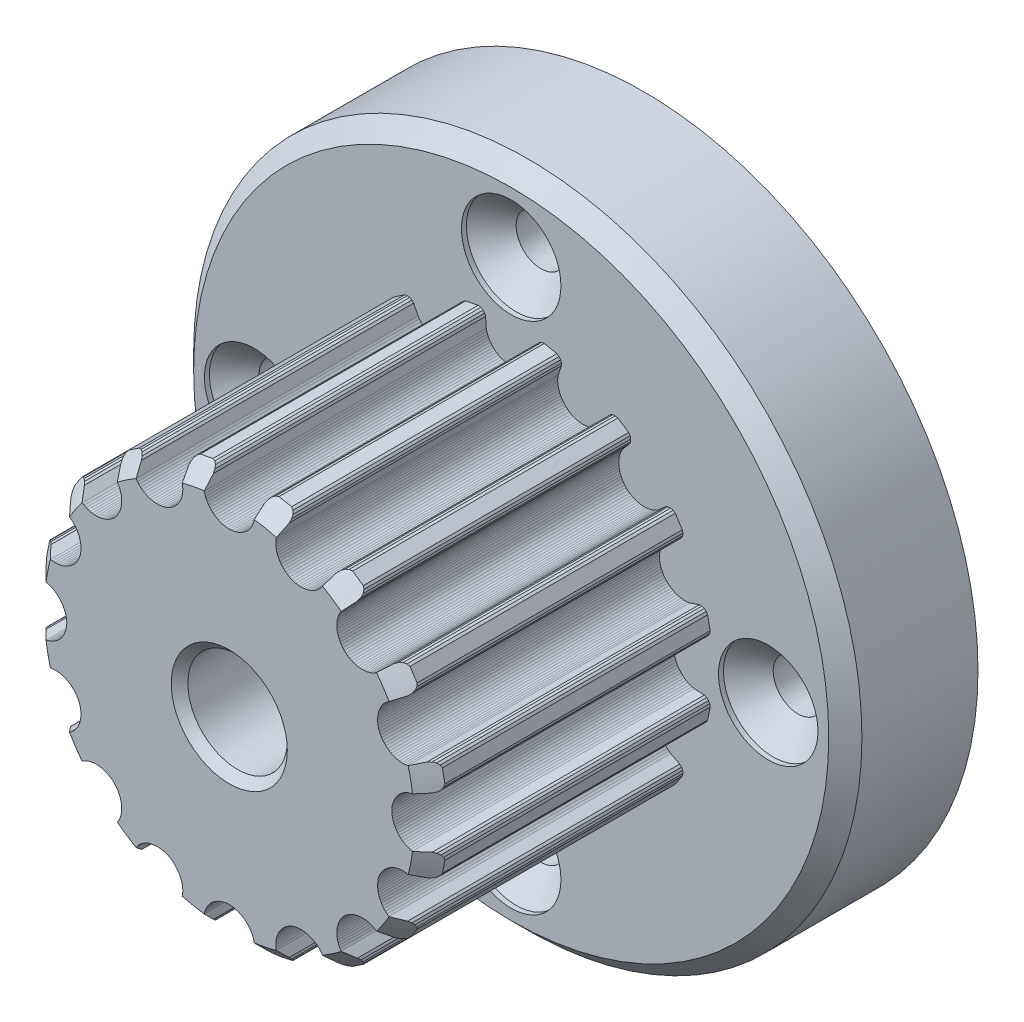
SolidWorks part; units mm, degrees
ref_plane "Front Plane" through (0, 0, 0) normal (0, 0, 1) x (1, 0, 0)
ref_plane "Top Plane" through (0, 0, 0) normal (0, 1, 0) x (1, 0, 0)
ref_plane "Right Plane" through (0, 0, 0) normal (1, 0, 0) x (0, 0, -1)
sketch "Sketch1" plane through (0, 0, 0) normal (0, 0, 1) x (1, 0, 0)
  circle A0 centre (0, 0) radius 15.5
  circle A1 centre (0, 15.5) radius 1.5
  circle A2 centre (15.5, 0) radius 1.5
  circle A3 centre (0, -15.5) radius 1.5
  circle A4 centre (-15.5, 0) radius 1.5
  circle A5 centre (0, 0) radius 20.15
  dimension "D1" = 31
  dimension "D2" = 3
  dimension "D3" = 40.3
extrude "Boss-Extrude1" add sketch "Sketch1" along normal blind 8 contours A5 A4 A0 A1 A2 A3 | A4 A0 A3 A2 A1 region at (0, 0, 0) region at (-19.5801, 0, 0)
sketch "Sketch8" plane through (0, 0, 8) normal (0, 0, 1) x (1, 0, 0)
  line L0 (-1.9904, -11.9969) -> (-1.8333, -11.9702)
  line L1 (-1.8333, -11.9702) -> (-1.6992, -11.8961)
  line L2 (-1.6992, -11.8961) -> (-1.5993, -11.7835)
  line L3 (-1.5993, -11.7835) -> (-1.5446, -11.6413)
  line L4 (-1.5446, -11.6413) -> (-1.5027, -11.0359)
  line L5 (-1.5027, -11.0359) -> (-1.4725, -10.9073)
  line L6 (-1.4725, -10.9073) -> (-1.4313, -10.7834)
  line L7 (-1.4313, -10.7834) -> (-1.3796, -10.6646)
  line L8 (-1.3796, -10.6646) -> (-1.3179, -10.5514)
  line L9 (-1.3179, -10.5514) -> (-1.2467, -10.4444)
  line L10 (-1.2467, -10.4444) -> (-1.1667, -10.3438)
  line L11 (-1.1667, -10.3438) -> (-1.0783, -10.2503)
  line L12 (-1.0783, -10.2503) -> (-0.9822, -10.1642)
  line L13 (-0.9822, -10.1642) -> (-0.8789, -10.086)
  line L14 (-0.8789, -10.086) -> (-0.7689, -10.0162)
  line L15 (-0.7689, -10.0162) -> (-0.6528, -9.9552)
  line L16 (-0.6528, -9.9552) -> (-0.5312, -9.9034)
  line L17 (-0.5312, -9.9034) -> (-0.4045, -9.8614)
  line L18 (-0.4045, -9.8614) -> (-0.2734, -9.8296)
  line L19 (-0.2734, -9.8296) -> (-0.1385, -9.8084)
  line L20 (-0.1385, -9.8084) -> (-0.0002, -9.7984)
  line L21 (-0.0002, -9.7984) -> (0.1382, -9.8084)
  line L22 (0.1382, -9.8084) -> (0.2733, -9.8295)
  line L23 (0.2733, -9.8295) -> (0.4045, -9.8613)
  line L24 (0.4045, -9.8613) -> (0.5312, -9.9032)
  line L25 (0.5312, -9.9032) -> (0.6529, -9.9549)
  line L26 (0.6529, -9.9549) -> (0.7691, -10.0159)
  line L27 (0.7691, -10.0159) -> (0.8791, -10.0858)
  line L28 (0.8791, -10.0858) -> (0.9825, -10.1639)
  line L29 (0.9825, -10.1639) -> (1.0786, -10.25)
  line L30 (1.0786, -10.25) -> (1.1669, -10.3436)
  line L31 (1.1669, -10.3436) -> (1.247, -10.4442)
  line L32 (1.247, -10.4442) -> (1.3181, -10.5512)
  line L33 (1.3181, -10.5512) -> (1.3798, -10.6644)
  line L34 (1.3798, -10.6644) -> (1.4315, -10.7832)
  line L35 (1.4315, -10.7832) -> (1.4726, -10.9072)
  line L36 (1.4726, -10.9072) -> (1.5027, -11.0359)
  line L37 (1.5027, -11.0359) -> (1.5446, -11.6413)
  line L38 (1.5446, -11.6413) -> (1.5993, -11.7835)
  line L39 (1.5993, -11.7835) -> (1.6992, -11.8961)
  line L40 (1.6992, -11.8961) -> (1.8333, -11.9702)
  line L41 (1.8333, -11.9702) -> (1.9904, -11.9969)
  line L42 (1.9904, -11.9969) -> (2.7522, -11.8454)
  line L43 (2.7522, -11.8454) -> (2.8871, -11.7606)
  line L44 (2.8871, -11.7606) -> (2.9825, -11.6408)
  line L45 (2.9825, -11.6408) -> (3.0317, -11.4985)
  line L46 (3.0317, -11.4985) -> (3.0279, -11.3462)
  line L47 (3.0279, -11.3462) -> (2.835, -10.7709)
  line L48 (2.835, -10.7709) -> (2.8136, -10.6405)
  line L49 (2.8136, -10.6405) -> (2.8042, -10.5103)
  line L50 (2.8042, -10.5103) -> (2.8066, -10.3807)
  line L51 (2.8066, -10.3807) -> (2.8203, -10.2526)
  line L52 (2.8203, -10.2526) -> (2.8451, -10.1264)
  line L53 (2.8451, -10.1264) -> (2.8805, -10.0029)
  line L54 (2.8805, -10.0029) -> (2.9264, -9.8827)
  line L55 (2.9264, -9.8827) -> (2.9822, -9.7664)
  line L56 (2.9822, -9.7664) -> (3.0478, -9.6546)
  line L57 (3.0478, -9.6546) -> (3.1227, -9.548)
  line L58 (3.1227, -9.548) -> (3.2066, -9.4472)
  line L59 (3.2066, -9.4472) -> (3.2992, -9.3528)
  line L60 (3.2992, -9.3528) -> (3.4001, -9.2656)
  line L61 (3.4001, -9.2656) -> (3.509, -9.186)
  line L62 (3.509, -9.186) -> (3.6256, -9.1148)
  line L63 (3.6256, -9.1148) -> (3.7495, -9.0526)
  line L64 (3.7495, -9.0526) -> (3.8812, -9.0089)
  line L65 (3.8812, -9.0089) -> (4.0141, -8.9767)
  line L66 (4.0141, -8.9767) -> (4.1474, -8.9558)
  line L67 (4.1474, -8.9558) -> (4.2806, -8.9461)
  line L68 (4.2806, -8.9461) -> (4.4128, -8.9473)
  line L69 (4.4128, -8.9473) -> (4.5435, -8.9592)
  line L70 (4.5435, -8.9592) -> (4.6718, -8.9816)
  line L71 (4.6718, -8.9816) -> (4.7972, -9.0143)
  line L72 (4.7972, -9.0143) -> (4.919, -9.057)
  line L73 (4.919, -9.057) -> (5.0364, -9.1097)
  line L74 (5.0364, -9.1097) -> (5.1488, -9.1719)
  line L75 (5.1488, -9.1719) -> (5.2555, -9.2437)
  line L76 (5.2555, -9.2437) -> (5.3558, -9.3246)
  line L77 (5.3558, -9.3246) -> (5.4491, -9.4146)
  line L78 (5.4491, -9.4146) -> (5.5345, -9.5134)
  line L79 (5.5345, -9.5134) -> (5.6115, -9.6208)
  line L80 (5.6115, -9.6208) -> (5.882, -10.164)
  line L81 (5.882, -10.164) -> (5.9869, -10.2745)
  line L82 (5.9869, -10.2745) -> (6.1223, -10.3403)
  line L83 (6.1223, -10.3403) -> (6.2745, -10.3575)
  line L84 (6.2745, -10.3575) -> (6.4299, -10.322)
  line L85 (6.4299, -10.322) -> (7.0757, -9.8905)
  line L86 (7.0757, -9.8905) -> (7.1679, -9.7605)
  line L87 (7.1679, -9.7605) -> (7.2103, -9.6133)
  line L88 (7.2103, -9.6133) -> (7.2013, -9.4631)
  line L89 (7.2013, -9.4631) -> (7.1394, -9.3238)
  line L90 (7.1394, -9.3238) -> (6.741, -8.8661)
  line L91 (6.741, -8.8661) -> (6.6714, -8.7539)
  line L92 (6.6714, -8.7539) -> (6.6129, -8.6371)
  line L93 (6.6129, -8.6371) -> (6.5655, -8.5165)
  line L94 (6.5655, -8.5165) -> (6.5291, -8.3929)
  line L95 (6.5291, -8.3929) -> (6.5037, -8.2669)
  line L96 (6.5037, -8.2669) -> (6.4892, -8.1392)
  line L97 (6.4892, -8.1392) -> (6.4856, -8.0106)
  line L98 (6.4856, -8.0106) -> (6.4926, -7.8817)
  line L99 (6.4926, -7.8817) -> (6.5104, -7.7534)
  line L100 (6.5104, -7.7534) -> (6.5388, -7.6262)
  line L101 (6.5388, -7.6262) -> (6.5778, -7.501)
  line L102 (6.5778, -7.501) -> (6.6272, -7.3784)
  line L103 (6.6272, -7.3784) -> (6.687, -7.2591)
  line L104 (6.687, -7.2591) -> (6.7572, -7.1439)
  line L105 (6.7572, -7.1439) -> (6.8377, -7.0335)
  line L106 (6.8377, -7.0335) -> (6.9284, -6.9286)
  line L107 (6.9284, -6.9286) -> (7.0333, -6.8378)
  line L108 (7.0333, -6.8378) -> (7.1438, -6.7572)
  line L109 (7.1438, -6.7572) -> (7.259, -6.6869)
  line L110 (7.259, -6.6869) -> (7.3783, -6.627)
  line L111 (7.3783, -6.627) -> (7.5009, -6.5775)
  line L112 (7.5009, -6.5775) -> (7.6262, -6.5385)
  line L113 (7.6262, -6.5385) -> (7.7533, -6.5101)
  line L114 (7.7533, -6.5101) -> (7.8817, -6.4923)
  line L115 (7.8817, -6.4923) -> (8.0105, -6.4852)
  line L116 (8.0105, -6.4852) -> (8.1392, -6.4889)
  line L117 (8.1392, -6.4889) -> (8.2669, -6.5034)
  line L118 (8.2669, -6.5034) -> (8.3929, -6.5288)
  line L119 (8.3929, -6.5288) -> (8.5165, -6.5652)
  line L120 (8.5165, -6.5652) -> (8.6371, -6.6127)
  line L121 (8.6371, -6.6127) -> (8.7539, -6.6713)
  line L122 (8.7539, -6.6713) -> (8.8661, -6.741)
  line L123 (8.8661, -6.741) -> (9.3238, -7.1394)
  line L124 (9.3238, -7.1394) -> (9.4631, -7.2013)
  line L125 (9.4631, -7.2013) -> (9.6133, -7.2103)
  line L126 (9.6133, -7.2103) -> (9.7605, -7.1679)
  line L127 (9.7605, -7.1679) -> (9.8905, -7.0757)
  line L128 (9.8905, -7.0757) -> (10.322, -6.4299)
  line L129 (10.322, -6.4299) -> (10.3575, -6.2745)
  line L130 (10.3575, -6.2745) -> (10.3403, -6.1223)
  line L131 (10.3403, -6.1223) -> (10.2745, -5.9869)
  line L132 (10.2745, -5.9869) -> (10.164, -5.882)
  line L133 (10.164, -5.882) -> (9.6208, -5.6115)
  line L134 (9.6208, -5.6115) -> (9.5135, -5.5345)
  line L135 (9.5135, -5.5345) -> (9.4148, -5.449)
  line L136 (9.4148, -5.449) -> (9.3248, -5.3558)
  line L137 (9.3248, -5.3558) -> (9.2439, -5.2554)
  line L138 (9.2439, -5.2554) -> (9.1722, -5.1487)
  line L139 (9.1722, -5.1487) -> (9.11, -5.0363)
  line L140 (9.11, -5.0363) -> (9.0574, -4.9189)
  line L141 (9.0574, -4.9189) -> (9.0146, -4.7971)
  line L142 (9.0146, -4.7971) -> (8.9819, -4.6717)
  line L143 (8.9819, -4.6717) -> (8.9595, -4.5434)
  line L144 (8.9595, -4.5434) -> (8.9476, -4.4128)
  line L145 (8.9476, -4.4128) -> (8.9463, -4.2806)
  line L146 (8.9463, -4.2806) -> (8.956, -4.1475)
  line L147 (8.956, -4.1475) -> (8.9767, -4.0143)
  line L148 (8.9767, -4.0143) -> (9.0088, -3.8815)
  line L149 (9.0088, -3.8815) -> (9.0524, -3.7498)
  line L150 (9.0524, -3.7498) -> (9.1147, -3.6258)
  line L151 (9.1147, -3.6258) -> (9.1859, -3.5091)
  line L152 (9.1859, -3.5091) -> (9.2654, -3.4)
  line L153 (9.2654, -3.4) -> (9.3527, -3.299)
  line L154 (9.3527, -3.299) -> (9.447, -3.2064)
  line L155 (9.447, -3.2064) -> (9.5478, -3.1224)
  line L156 (9.5478, -3.1224) -> (9.6544, -3.0475)
  line L157 (9.6544, -3.0475) -> (9.7662, -2.9819)
  line L158 (9.7662, -2.9819) -> (9.8826, -2.926)
  line L159 (9.8826, -2.926) -> (10.0028, -2.8802)
  line L160 (10.0028, -2.8802) -> (10.1263, -2.8448)
  line L161 (10.1263, -2.8448) -> (10.2525, -2.82)
  line L162 (10.2525, -2.82) -> (10.3807, -2.8064)
  line L163 (10.3807, -2.8064) -> (10.5102, -2.8041)
  line L164 (10.5102, -2.8041) -> (10.6405, -2.8135)
  line L165 (10.6405, -2.8135) -> (10.7709, -2.835)
  line L166 (10.7709, -2.835) -> (11.3462, -3.0279)
  line L167 (11.3462, -3.0279) -> (11.4985, -3.0317)
  line L168 (11.4985, -3.0317) -> (11.6408, -2.9825)
  line L169 (11.6408, -2.9825) -> (11.7606, -2.8871)
  line L170 (11.7606, -2.8871) -> (11.8454, -2.7522)
  line L171 (11.8454, -2.7522) -> (11.9969, -1.9904)
  line L172 (11.9969, -1.9904) -> (11.9702, -1.8333)
  line L173 (11.9702, -1.8333) -> (11.8961, -1.6992)
  line L174 (11.8961, -1.6992) -> (11.7835, -1.5993)
  line L175 (11.7835, -1.5993) -> (11.6413, -1.5446)
  line L176 (11.6413, -1.5446) -> (11.0359, -1.5027)
  line L177 (11.0359, -1.5027) -> (10.9073, -1.4725)
  line L178 (10.9073, -1.4725) -> (10.7834, -1.4313)
  line L179 (10.7834, -1.4313) -> (10.6646, -1.3796)
  line L180 (10.6646, -1.3796) -> (10.5514, -1.3179)
  line L181 (10.5514, -1.3179) -> (10.4444, -1.2467)
  line L182 (10.4444, -1.2467) -> (10.3438, -1.1667)
  line L183 (10.3438, -1.1667) -> (10.2503, -1.0783)
  line L184 (10.2503, -1.0783) -> (10.1642, -0.9822)
  line L185 (10.1642, -0.9822) -> (10.086, -0.8789)
  line L186 (10.086, -0.8789) -> (10.0162, -0.7689)
  line L187 (10.0162, -0.7689) -> (9.9552, -0.6528)
  line L188 (9.9552, -0.6528) -> (9.9034, -0.5312)
  line L189 (9.9034, -0.5312) -> (9.8614, -0.4045)
  line L190 (9.8614, -0.4045) -> (9.8296, -0.2734)
  line L191 (9.8296, -0.2734) -> (9.8084, -0.1385)
  line L192 (9.8084, -0.1385) -> (9.7984, -0.0002)
  line L193 (9.7984, -0.0002) -> (9.8084, 0.1382)
  line L194 (9.8084, 0.1382) -> (9.8295, 0.2733)
  line L195 (9.8295, 0.2733) -> (9.8613, 0.4045)
  line L196 (9.8613, 0.4045) -> (9.9032, 0.5312)
  line L197 (9.9032, 0.5312) -> (9.9549, 0.6529)
  line L198 (9.9549, 0.6529) -> (10.0159, 0.7691)
  line L199 (10.0159, 0.7691) -> (10.0858, 0.8791)
  line L200 (10.0858, 0.8791) -> (10.1639, 0.9825)
  line L201 (10.1639, 0.9825) -> (10.25, 1.0786)
  line L202 (10.25, 1.0786) -> (10.3436, 1.1669)
  line L203 (10.3436, 1.1669) -> (10.4442, 1.247)
  line L204 (10.4442, 1.247) -> (10.5512, 1.3181)
  line L205 (10.5512, 1.3181) -> (10.6644, 1.3798)
  line L206 (10.6644, 1.3798) -> (10.7832, 1.4315)
  line L207 (10.7832, 1.4315) -> (10.9072, 1.4726)
  line L208 (10.9072, 1.4726) -> (11.0359, 1.5027)
  line L209 (11.0359, 1.5027) -> (11.6413, 1.5446)
  line L210 (11.6413, 1.5446) -> (11.7835, 1.5993)
  line L211 (11.7835, 1.5993) -> (11.8961, 1.6992)
  line L212 (11.8961, 1.6992) -> (11.9702, 1.8333)
  line L213 (11.9702, 1.8333) -> (11.9969, 1.9904)
  line L214 (11.9969, 1.9904) -> (11.8454, 2.7522)
  line L215 (11.8454, 2.7522) -> (11.7606, 2.8871)
  line L216 (11.7606, 2.8871) -> (11.6408, 2.9825)
  line L217 (11.6408, 2.9825) -> (11.4985, 3.0317)
  line L218 (11.4985, 3.0317) -> (11.3462, 3.0279)
  line L219 (11.3462, 3.0279) -> (10.7709, 2.835)
  line L220 (10.7709, 2.835) -> (10.6405, 2.8136)
  line L221 (10.6405, 2.8136) -> (10.5103, 2.8042)
  line L222 (10.5103, 2.8042) -> (10.3807, 2.8066)
  line L223 (10.3807, 2.8066) -> (10.2526, 2.8203)
  line L224 (10.2526, 2.8203) -> (10.1264, 2.8451)
  line L225 (10.1264, 2.8451) -> (10.0029, 2.8805)
  line L226 (10.0029, 2.8805) -> (9.8827, 2.9264)
  line L227 (9.8827, 2.9264) -> (9.7664, 2.9822)
  line L228 (9.7664, 2.9822) -> (9.6546, 3.0478)
  line L229 (9.6546, 3.0478) -> (9.548, 3.1227)
  line L230 (9.548, 3.1227) -> (9.4472, 3.2066)
  line L231 (9.4472, 3.2066) -> (9.3528, 3.2992)
  line L232 (9.3528, 3.2992) -> (9.2656, 3.4001)
  line L233 (9.2656, 3.4001) -> (9.186, 3.509)
  line L234 (9.186, 3.509) -> (9.1148, 3.6256)
  line L235 (9.1148, 3.6256) -> (9.0526, 3.7495)
  line L236 (9.0526, 3.7495) -> (9.0089, 3.8812)
  line L237 (9.0089, 3.8812) -> (8.9767, 4.0141)
  line L238 (8.9767, 4.0141) -> (8.9558, 4.1474)
  line L239 (8.9558, 4.1474) -> (8.9461, 4.2806)
  line L240 (8.9461, 4.2806) -> (8.9473, 4.4128)
  line L241 (8.9473, 4.4128) -> (8.9592, 4.5435)
  line L242 (8.9592, 4.5435) -> (8.9816, 4.6718)
  line L243 (8.9816, 4.6718) -> (9.0143, 4.7972)
  line L244 (9.0143, 4.7972) -> (9.057, 4.919)
  line L245 (9.057, 4.919) -> (9.1097, 5.0364)
  line L246 (9.1097, 5.0364) -> (9.1719, 5.1488)
  line L247 (9.1719, 5.1488) -> (9.2437, 5.2555)
  line L248 (9.2437, 5.2555) -> (9.3246, 5.3558)
  line L249 (9.3246, 5.3558) -> (9.4146, 5.4491)
  line L250 (9.4146, 5.4491) -> (9.5134, 5.5345)
  line L251 (9.5134, 5.5345) -> (9.6208, 5.6115)
  line L252 (9.6208, 5.6115) -> (10.164, 5.882)
  line L253 (10.164, 5.882) -> (10.2745, 5.9869)
  line L254 (10.2745, 5.9869) -> (10.3403, 6.1223)
  line L255 (10.3403, 6.1223) -> (10.3575, 6.2745)
  line L256 (10.3575, 6.2745) -> (10.322, 6.4299)
  line L257 (10.322, 6.4299) -> (9.8905, 7.0757)
  line L258 (9.8905, 7.0757) -> (9.7605, 7.1679)
  line L259 (9.7605, 7.1679) -> (9.6133, 7.2103)
  line L260 (9.6133, 7.2103) -> (9.4631, 7.2013)
  line L261 (9.4631, 7.2013) -> (9.3238, 7.1394)
  line L262 (9.3238, 7.1394) -> (8.8661, 6.741)
  line L263 (8.8661, 6.741) -> (8.7539, 6.6714)
  line L264 (8.7539, 6.6714) -> (8.6371, 6.6129)
  line L265 (8.6371, 6.6129) -> (8.5165, 6.5655)
  line L266 (8.5165, 6.5655) -> (8.3929, 6.5291)
  line L267 (8.3929, 6.5291) -> (8.2669, 6.5037)
  line L268 (8.2669, 6.5037) -> (8.1392, 6.4892)
  line L269 (8.1392, 6.4892) -> (8.0106, 6.4856)
  line L270 (8.0106, 6.4856) -> (7.8817, 6.4926)
  line L271 (7.8817, 6.4926) -> (7.7534, 6.5104)
  line L272 (7.7534, 6.5104) -> (7.6262, 6.5388)
  line L273 (7.6262, 6.5388) -> (7.501, 6.5778)
  line L274 (7.501, 6.5778) -> (7.3784, 6.6272)
  line L275 (7.3784, 6.6272) -> (7.2591, 6.687)
  line L276 (7.2591, 6.687) -> (7.1439, 6.7572)
  line L277 (7.1439, 6.7572) -> (7.0335, 6.8377)
  line L278 (7.0335, 6.8377) -> (6.9286, 6.9284)
  line L279 (6.9286, 6.9284) -> (6.8378, 7.0333)
  line L280 (6.8378, 7.0333) -> (6.7572, 7.1438)
  line L281 (6.7572, 7.1438) -> (6.6869, 7.259)
  line L282 (6.6869, 7.259) -> (6.627, 7.3783)
  line L283 (6.627, 7.3783) -> (6.5775, 7.5009)
  line L284 (6.5775, 7.5009) -> (6.5385, 7.6262)
  line L285 (6.5385, 7.6262) -> (6.5101, 7.7533)
  line L286 (6.5101, 7.7533) -> (6.4923, 7.8817)
  line L287 (6.4923, 7.8817) -> (6.4852, 8.0105)
  line L288 (6.4852, 8.0105) -> (6.4889, 8.1392)
  line L289 (6.4889, 8.1392) -> (6.5034, 8.2669)
  line L290 (6.5034, 8.2669) -> (6.5288, 8.3929)
  line L291 (6.5288, 8.3929) -> (6.5652, 8.5165)
  line L292 (6.5652, 8.5165) -> (6.6127, 8.6371)
  line L293 (6.6127, 8.6371) -> (6.6713, 8.7539)
  line L294 (6.6713, 8.7539) -> (6.741, 8.8661)
  line L295 (6.741, 8.8661) -> (7.1394, 9.3238)
  line L296 (7.1394, 9.3238) -> (7.2013, 9.4631)
  line L297 (7.2013, 9.4631) -> (7.2103, 9.6133)
  line L298 (7.2103, 9.6133) -> (7.1679, 9.7605)
  line L299 (7.1679, 9.7605) -> (7.0757, 9.8905)
  line L300 (7.0757, 9.8905) -> (6.4299, 10.322)
  line L301 (6.4299, 10.322) -> (6.2745, 10.3575)
  line L302 (6.2745, 10.3575) -> (6.1223, 10.3403)
  line L303 (6.1223, 10.3403) -> (5.9869, 10.2745)
  line L304 (5.9869, 10.2745) -> (5.882, 10.164)
  line L305 (5.882, 10.164) -> (5.6115, 9.6208)
  line L306 (5.6115, 9.6208) -> (5.5345, 9.5135)
  line L307 (5.5345, 9.5135) -> (5.449, 9.4148)
  line L308 (5.449, 9.4148) -> (5.3558, 9.3248)
  line L309 (5.3558, 9.3248) -> (5.2554, 9.2439)
  line L310 (5.2554, 9.2439) -> (5.1487, 9.1722)
  line L311 (5.1487, 9.1722) -> (5.0363, 9.11)
  line L312 (5.0363, 9.11) -> (4.9189, 9.0574)
  line L313 (4.9189, 9.0574) -> (4.7971, 9.0146)
  line L314 (4.7971, 9.0146) -> (4.6717, 8.9819)
  line L315 (4.6717, 8.9819) -> (4.5434, 8.9595)
  line L316 (4.5434, 8.9595) -> (4.4128, 8.9476)
  line L317 (4.4128, 8.9476) -> (4.2806, 8.9463)
  line L318 (4.2806, 8.9463) -> (4.1475, 8.956)
  line L319 (4.1475, 8.956) -> (4.0143, 8.9767)
  line L320 (4.0143, 8.9767) -> (3.8815, 9.0088)
  line L321 (3.8815, 9.0088) -> (3.7498, 9.0524)
  line L322 (3.7498, 9.0524) -> (3.6258, 9.1147)
  line L323 (3.6258, 9.1147) -> (3.5091, 9.1859)
  line L324 (3.5091, 9.1859) -> (3.4, 9.2654)
  line L325 (3.4, 9.2654) -> (3.299, 9.3527)
  line L326 (3.299, 9.3527) -> (3.2064, 9.447)
  line L327 (3.2064, 9.447) -> (3.1224, 9.5478)
  line L328 (3.1224, 9.5478) -> (3.0475, 9.6544)
  line L329 (3.0475, 9.6544) -> (2.9819, 9.7662)
  line L330 (2.9819, 9.7662) -> (2.926, 9.8826)
  line L331 (2.926, 9.8826) -> (2.8802, 10.0028)
  line L332 (2.8802, 10.0028) -> (2.8448, 10.1263)
  line L333 (2.8448, 10.1263) -> (2.82, 10.2525)
  line L334 (2.82, 10.2525) -> (2.8064, 10.3807)
  line L335 (2.8064, 10.3807) -> (2.8041, 10.5102)
  line L336 (2.8041, 10.5102) -> (2.8135, 10.6405)
  line L337 (2.8135, 10.6405) -> (2.835, 10.7709)
  line L338 (2.835, 10.7709) -> (3.0279, 11.3462)
  line L339 (3.0279, 11.3462) -> (3.0317, 11.4985)
  line L340 (3.0317, 11.4985) -> (2.9825, 11.6408)
  line L341 (2.9825, 11.6408) -> (2.8871, 11.7606)
  line L342 (2.8871, 11.7606) -> (2.7522, 11.8454)
  line L343 (2.7522, 11.8454) -> (1.9904, 11.9969)
  line L344 (1.9904, 11.9969) -> (1.8333, 11.9702)
  line L345 (1.8333, 11.9702) -> (1.6992, 11.8961)
  line L346 (1.6992, 11.8961) -> (1.5993, 11.7835)
  line L347 (1.5993, 11.7835) -> (1.5446, 11.6413)
  line L348 (1.5446, 11.6413) -> (1.5027, 11.0359)
  line L349 (1.5027, 11.0359) -> (1.4725, 10.9073)
  line L350 (1.4725, 10.9073) -> (1.4313, 10.7834)
  line L351 (1.4313, 10.7834) -> (1.3796, 10.6646)
  line L352 (1.3796, 10.6646) -> (1.3179, 10.5514)
  line L353 (1.3179, 10.5514) -> (1.2467, 10.4444)
  line L354 (1.2467, 10.4444) -> (1.1667, 10.3438)
  line L355 (1.1667, 10.3438) -> (1.0783, 10.2503)
  line L356 (1.0783, 10.2503) -> (0.9822, 10.1642)
  line L357 (0.9822, 10.1642) -> (0.8789, 10.086)
  line L358 (0.8789, 10.086) -> (0.7689, 10.0162)
  line L359 (0.7689, 10.0162) -> (0.6528, 9.9552)
  line L360 (0.6528, 9.9552) -> (0.5312, 9.9034)
  line L361 (0.5312, 9.9034) -> (0.4045, 9.8614)
  line L362 (0.4045, 9.8614) -> (0.2734, 9.8296)
  line L363 (0.2734, 9.8296) -> (0.1385, 9.8084)
  line L364 (0.1385, 9.8084) -> (0.0002, 9.7984)
  line L365 (0.0002, 9.7984) -> (-0.1382, 9.8084)
  line L366 (-0.1382, 9.8084) -> (-0.2733, 9.8295)
  line L367 (-0.2733, 9.8295) -> (-0.4045, 9.8613)
  line L368 (-0.4045, 9.8613) -> (-0.5312, 9.9032)
  line L369 (-0.5312, 9.9032) -> (-0.6529, 9.9549)
  line L370 (-0.6529, 9.9549) -> (-0.7691, 10.0159)
  line L371 (-0.7691, 10.0159) -> (-0.8791, 10.0858)
  line L372 (-0.8791, 10.0858) -> (-0.9825, 10.1639)
  line L373 (-0.9825, 10.1639) -> (-1.0786, 10.25)
  line L374 (-1.0786, 10.25) -> (-1.1669, 10.3436)
  line L375 (-1.1669, 10.3436) -> (-1.247, 10.4442)
  line L376 (-1.247, 10.4442) -> (-1.3181, 10.5512)
  line L377 (-1.3181, 10.5512) -> (-1.3798, 10.6644)
  line L378 (-1.3798, 10.6644) -> (-1.4315, 10.7832)
  line L379 (-1.4315, 10.7832) -> (-1.4726, 10.9072)
  line L380 (-1.4726, 10.9072) -> (-1.5027, 11.0359)
  line L381 (-1.5027, 11.0359) -> (-1.5446, 11.6413)
  line L382 (-1.5446, 11.6413) -> (-1.5993, 11.7835)
  line L383 (-1.5993, 11.7835) -> (-1.6992, 11.8961)
  line L384 (-1.6992, 11.8961) -> (-1.8333, 11.9702)
  line L385 (-1.8333, 11.9702) -> (-1.9904, 11.9969)
  line L386 (-1.9904, 11.9969) -> (-2.7522, 11.8454)
  line L387 (-2.7522, 11.8454) -> (-2.8871, 11.7606)
  line L388 (-2.8871, 11.7606) -> (-2.9825, 11.6408)
  line L389 (-2.9825, 11.6408) -> (-3.0317, 11.4985)
  line L390 (-3.0317, 11.4985) -> (-3.0279, 11.3462)
  line L391 (-3.0279, 11.3462) -> (-2.835, 10.7709)
  line L392 (-2.835, 10.7709) -> (-2.8136, 10.6405)
  line L393 (-2.8136, 10.6405) -> (-2.8042, 10.5103)
  line L394 (-2.8042, 10.5103) -> (-2.8066, 10.3807)
  line L395 (-2.8066, 10.3807) -> (-2.8203, 10.2526)
  line L396 (-2.8203, 10.2526) -> (-2.8451, 10.1264)
  line L397 (-2.8451, 10.1264) -> (-2.8805, 10.0029)
  line L398 (-2.8805, 10.0029) -> (-2.9264, 9.8827)
  line L399 (-2.9264, 9.8827) -> (-2.9822, 9.7664)
  line L400 (-2.9822, 9.7664) -> (-3.0478, 9.6546)
  line L401 (-3.0478, 9.6546) -> (-3.1227, 9.548)
  line L402 (-3.1227, 9.548) -> (-3.2066, 9.4472)
  line L403 (-3.2066, 9.4472) -> (-3.2992, 9.3528)
  line L404 (-3.2992, 9.3528) -> (-3.4001, 9.2656)
  line L405 (-3.4001, 9.2656) -> (-3.509, 9.186)
  line L406 (-3.509, 9.186) -> (-3.6256, 9.1148)
  line L407 (-3.6256, 9.1148) -> (-3.7495, 9.0526)
  line L408 (-3.7495, 9.0526) -> (-3.8812, 9.0089)
  line L409 (-3.8812, 9.0089) -> (-4.0141, 8.9767)
  line L410 (-4.0141, 8.9767) -> (-4.1474, 8.9558)
  line L411 (-4.1474, 8.9558) -> (-4.2806, 8.9461)
  line L412 (-4.2806, 8.9461) -> (-4.4128, 8.9473)
  line L413 (-4.4128, 8.9473) -> (-4.5435, 8.9592)
  line L414 (-4.5435, 8.9592) -> (-4.6718, 8.9816)
  line L415 (-4.6718, 8.9816) -> (-4.7972, 9.0143)
  line L416 (-4.7972, 9.0143) -> (-4.919, 9.057)
  line L417 (-4.919, 9.057) -> (-5.0364, 9.1097)
  line L418 (-5.0364, 9.1097) -> (-5.1488, 9.1719)
  line L419 (-5.1488, 9.1719) -> (-5.2555, 9.2437)
  line L420 (-5.2555, 9.2437) -> (-5.3558, 9.3246)
  line L421 (-5.3558, 9.3246) -> (-5.4491, 9.4146)
  line L422 (-5.4491, 9.4146) -> (-5.5345, 9.5134)
  line L423 (-5.5345, 9.5134) -> (-5.6115, 9.6208)
  line L424 (-5.6115, 9.6208) -> (-5.882, 10.164)
  line L425 (-5.882, 10.164) -> (-5.9869, 10.2745)
  line L426 (-5.9869, 10.2745) -> (-6.1223, 10.3403)
  line L427 (-6.1223, 10.3403) -> (-6.2745, 10.3575)
  line L428 (-6.2745, 10.3575) -> (-6.4299, 10.322)
  line L429 (-6.4299, 10.322) -> (-7.0757, 9.8905)
  line L430 (-7.0757, 9.8905) -> (-7.1679, 9.7605)
  line L431 (-7.1679, 9.7605) -> (-7.2103, 9.6133)
  line L432 (-7.2103, 9.6133) -> (-7.2013, 9.4631)
  line L433 (-7.2013, 9.4631) -> (-7.1394, 9.3238)
  line L434 (-7.1394, 9.3238) -> (-6.741, 8.8661)
  line L435 (-6.741, 8.8661) -> (-6.6714, 8.7539)
  line L436 (-6.6714, 8.7539) -> (-6.6129, 8.6371)
  line L437 (-6.6129, 8.6371) -> (-6.5655, 8.5165)
  line L438 (-6.5655, 8.5165) -> (-6.5291, 8.3929)
  line L439 (-6.5291, 8.3929) -> (-6.5037, 8.2669)
  line L440 (-6.5037, 8.2669) -> (-6.4892, 8.1392)
  line L441 (-6.4892, 8.1392) -> (-6.4856, 8.0106)
  line L442 (-6.4856, 8.0106) -> (-6.4926, 7.8817)
  line L443 (-6.4926, 7.8817) -> (-6.5104, 7.7534)
  line L444 (-6.5104, 7.7534) -> (-6.5388, 7.6262)
  line L445 (-6.5388, 7.6262) -> (-6.5778, 7.501)
  line L446 (-6.5778, 7.501) -> (-6.6272, 7.3784)
  line L447 (-6.6272, 7.3784) -> (-6.687, 7.2591)
  line L448 (-6.687, 7.2591) -> (-6.7572, 7.1439)
  line L449 (-6.7572, 7.1439) -> (-6.8377, 7.0335)
  line L450 (-6.8377, 7.0335) -> (-6.9284, 6.9286)
  line L451 (-6.9284, 6.9286) -> (-7.0333, 6.8378)
  line L452 (-7.0333, 6.8378) -> (-7.1438, 6.7572)
  line L453 (-7.1438, 6.7572) -> (-7.259, 6.6869)
  line L454 (-7.259, 6.6869) -> (-7.3783, 6.627)
  line L455 (-7.3783, 6.627) -> (-7.5009, 6.5775)
  line L456 (-7.5009, 6.5775) -> (-7.6262, 6.5385)
  line L457 (-7.6262, 6.5385) -> (-7.7533, 6.5101)
  line L458 (-7.7533, 6.5101) -> (-7.8817, 6.4923)
  line L459 (-7.8817, 6.4923) -> (-8.0105, 6.4852)
  line L460 (-8.0105, 6.4852) -> (-8.1392, 6.4889)
  line L461 (-8.1392, 6.4889) -> (-8.2669, 6.5034)
  line L462 (-8.2669, 6.5034) -> (-8.3929, 6.5288)
  line L463 (-8.3929, 6.5288) -> (-8.5165, 6.5652)
  line L464 (-8.5165, 6.5652) -> (-8.6371, 6.6127)
  line L465 (-8.6371, 6.6127) -> (-8.7539, 6.6713)
  line L466 (-8.7539, 6.6713) -> (-8.8661, 6.741)
  line L467 (-8.8661, 6.741) -> (-9.3238, 7.1394)
  line L468 (-9.3238, 7.1394) -> (-9.4631, 7.2013)
  line L469 (-9.4631, 7.2013) -> (-9.6133, 7.2103)
  line L470 (-9.6133, 7.2103) -> (-9.7605, 7.1679)
  line L471 (-9.7605, 7.1679) -> (-9.8905, 7.0757)
  line L472 (-9.8905, 7.0757) -> (-10.322, 6.4299)
  line L473 (-10.322, 6.4299) -> (-10.3575, 6.2745)
  line L474 (-10.3575, 6.2745) -> (-10.3403, 6.1223)
  line L475 (-10.3403, 6.1223) -> (-10.2745, 5.9869)
  line L476 (-10.2745, 5.9869) -> (-10.164, 5.882)
  line L477 (-10.164, 5.882) -> (-9.6208, 5.6115)
  line L478 (-9.6208, 5.6115) -> (-9.5135, 5.5345)
  line L479 (-9.5135, 5.5345) -> (-9.4148, 5.449)
  line L480 (-9.4148, 5.449) -> (-9.3248, 5.3558)
  line L481 (-9.3248, 5.3558) -> (-9.2439, 5.2554)
  line L482 (-9.2439, 5.2554) -> (-9.1722, 5.1487)
  line L483 (-9.1722, 5.1487) -> (-9.11, 5.0363)
  line L484 (-9.11, 5.0363) -> (-9.0574, 4.9189)
  line L485 (-9.0574, 4.9189) -> (-9.0146, 4.7971)
  line L486 (-9.0146, 4.7971) -> (-8.9819, 4.6717)
  line L487 (-8.9819, 4.6717) -> (-8.9595, 4.5434)
  line L488 (-8.9595, 4.5434) -> (-8.9476, 4.4128)
  line L489 (-8.9476, 4.4128) -> (-8.9463, 4.2806)
  line L490 (-8.9463, 4.2806) -> (-8.956, 4.1475)
  line L491 (-8.956, 4.1475) -> (-8.9767, 4.0143)
  line L492 (-8.9767, 4.0143) -> (-9.0088, 3.8815)
  line L493 (-9.0088, 3.8815) -> (-9.0524, 3.7498)
  line L494 (-9.0524, 3.7498) -> (-9.1147, 3.6258)
  line L495 (-9.1147, 3.6258) -> (-9.1859, 3.5091)
  line L496 (-9.1859, 3.5091) -> (-9.2654, 3.4)
  line L497 (-9.2654, 3.4) -> (-9.3527, 3.299)
  line L498 (-9.3527, 3.299) -> (-9.447, 3.2064)
  line L499 (-9.447, 3.2064) -> (-9.5478, 3.1224)
  line L500 (-9.5478, 3.1224) -> (-9.6544, 3.0475)
  line L501 (-9.6544, 3.0475) -> (-9.7662, 2.9819)
  line L502 (-9.7662, 2.9819) -> (-9.8826, 2.926)
  line L503 (-9.8826, 2.926) -> (-10.0028, 2.8802)
  line L504 (-10.0028, 2.8802) -> (-10.1263, 2.8448)
  line L505 (-10.1263, 2.8448) -> (-10.2525, 2.82)
  line L506 (-10.2525, 2.82) -> (-10.3807, 2.8064)
  line L507 (-10.3807, 2.8064) -> (-10.5102, 2.8041)
  line L508 (-10.5102, 2.8041) -> (-10.6405, 2.8135)
  line L509 (-10.6405, 2.8135) -> (-10.7709, 2.835)
  line L510 (-10.7709, 2.835) -> (-11.3462, 3.0279)
  line L511 (-11.3462, 3.0279) -> (-11.4985, 3.0317)
  line L512 (-11.4985, 3.0317) -> (-11.6408, 2.9825)
  line L513 (-11.6408, 2.9825) -> (-11.7606, 2.8871)
  line L514 (-11.7606, 2.8871) -> (-11.8454, 2.7522)
  line L515 (-11.8454, 2.7522) -> (-11.9969, 1.9904)
  line L516 (-11.9969, 1.9904) -> (-11.9702, 1.8333)
  line L517 (-11.9702, 1.8333) -> (-11.8961, 1.6992)
  line L518 (-11.8961, 1.6992) -> (-11.7835, 1.5993)
  line L519 (-11.7835, 1.5993) -> (-11.6413, 1.5446)
  line L520 (-11.6413, 1.5446) -> (-11.0359, 1.5027)
  line L521 (-11.0359, 1.5027) -> (-10.9073, 1.4725)
  line L522 (-10.9073, 1.4725) -> (-10.7834, 1.4313)
  line L523 (-10.7834, 1.4313) -> (-10.6646, 1.3796)
  line L524 (-10.6646, 1.3796) -> (-10.5514, 1.3179)
  line L525 (-10.5514, 1.3179) -> (-10.4444, 1.2467)
  line L526 (-10.4444, 1.2467) -> (-10.3438, 1.1667)
  line L527 (-10.3438, 1.1667) -> (-10.2503, 1.0783)
  line L528 (-10.2503, 1.0783) -> (-10.1642, 0.9822)
  line L529 (-10.1642, 0.9822) -> (-10.086, 0.8789)
  line L530 (-10.086, 0.8789) -> (-10.0162, 0.7689)
  line L531 (-10.0162, 0.7689) -> (-9.9552, 0.6528)
  line L532 (-9.9552, 0.6528) -> (-9.9034, 0.5312)
  line L533 (-9.9034, 0.5312) -> (-9.8614, 0.4045)
  line L534 (-9.8614, 0.4045) -> (-9.8296, 0.2734)
  line L535 (-9.8296, 0.2734) -> (-9.8084, 0.1385)
  line L536 (-9.8084, 0.1385) -> (-9.7984, 0.0002)
  line L537 (-9.7984, 0.0002) -> (-9.8084, -0.1382)
  line L538 (-9.8084, -0.1382) -> (-9.8295, -0.2733)
  line L539 (-9.8295, -0.2733) -> (-9.8613, -0.4045)
  line L540 (-9.8613, -0.4045) -> (-9.9032, -0.5312)
  line L541 (-9.9032, -0.5312) -> (-9.9549, -0.6529)
  line L542 (-9.9549, -0.6529) -> (-10.0159, -0.7691)
  line L543 (-10.0159, -0.7691) -> (-10.0858, -0.8791)
  line L544 (-10.0858, -0.8791) -> (-10.1639, -0.9825)
  line L545 (-10.1639, -0.9825) -> (-10.25, -1.0786)
  line L546 (-10.25, -1.0786) -> (-10.3436, -1.1669)
  line L547 (-10.3436, -1.1669) -> (-10.4442, -1.247)
  line L548 (-10.4442, -1.247) -> (-10.5512, -1.3181)
  line L549 (-10.5512, -1.3181) -> (-10.6644, -1.3798)
  line L550 (-10.6644, -1.3798) -> (-10.7832, -1.4315)
  line L551 (-10.7832, -1.4315) -> (-10.9072, -1.4726)
  line L552 (-10.9072, -1.4726) -> (-11.0359, -1.5027)
  line L553 (-11.0359, -1.5027) -> (-11.6413, -1.5446)
  line L554 (-11.6413, -1.5446) -> (-11.7835, -1.5993)
  line L555 (-11.7835, -1.5993) -> (-11.8961, -1.6992)
  line L556 (-11.8961, -1.6992) -> (-11.9702, -1.8333)
  line L557 (-11.9702, -1.8333) -> (-11.9969, -1.9904)
  line L558 (-11.9969, -1.9904) -> (-11.8454, -2.7522)
  line L559 (-11.8454, -2.7522) -> (-11.7606, -2.8871)
  line L560 (-11.7606, -2.8871) -> (-11.6408, -2.9825)
  line L561 (-11.6408, -2.9825) -> (-11.4985, -3.0317)
  line L562 (-11.4985, -3.0317) -> (-11.3462, -3.0279)
  line L563 (-11.3462, -3.0279) -> (-10.7709, -2.835)
  line L564 (-10.7709, -2.835) -> (-10.6405, -2.8136)
  line L565 (-10.6405, -2.8136) -> (-10.5103, -2.8042)
  line L566 (-10.5103, -2.8042) -> (-10.3807, -2.8066)
  line L567 (-10.3807, -2.8066) -> (-10.2526, -2.8203)
  line L568 (-10.2526, -2.8203) -> (-10.1264, -2.8451)
  line L569 (-10.1264, -2.8451) -> (-10.0029, -2.8805)
  line L570 (-10.0029, -2.8805) -> (-9.8827, -2.9264)
  line L571 (-9.8827, -2.9264) -> (-9.7664, -2.9822)
  line L572 (-9.7664, -2.9822) -> (-9.6546, -3.0478)
  line L573 (-9.6546, -3.0478) -> (-9.548, -3.1227)
  line L574 (-9.548, -3.1227) -> (-9.4472, -3.2066)
  line L575 (-9.4472, -3.2066) -> (-9.3528, -3.2992)
  line L576 (-9.3528, -3.2992) -> (-9.2656, -3.4001)
  line L577 (-9.2656, -3.4001) -> (-9.186, -3.509)
  line L578 (-9.186, -3.509) -> (-9.1148, -3.6256)
  line L579 (-9.1148, -3.6256) -> (-9.0526, -3.7495)
  line L580 (-9.0526, -3.7495) -> (-9.0089, -3.8812)
  line L581 (-9.0089, -3.8812) -> (-8.9767, -4.0141)
  line L582 (-8.9767, -4.0141) -> (-8.9558, -4.1474)
  line L583 (-8.9558, -4.1474) -> (-8.9461, -4.2806)
  line L584 (-8.9461, -4.2806) -> (-8.9473, -4.4128)
  line L585 (-8.9473, -4.4128) -> (-8.9592, -4.5435)
  line L586 (-8.9592, -4.5435) -> (-8.9816, -4.6718)
  line L587 (-8.9816, -4.6718) -> (-9.0143, -4.7972)
  line L588 (-9.0143, -4.7972) -> (-9.057, -4.919)
  line L589 (-9.057, -4.919) -> (-9.1097, -5.0364)
  line L590 (-9.1097, -5.0364) -> (-9.1719, -5.1488)
  line L591 (-9.1719, -5.1488) -> (-9.2437, -5.2555)
  line L592 (-9.2437, -5.2555) -> (-9.3246, -5.3558)
  line L593 (-9.3246, -5.3558) -> (-9.4146, -5.4491)
  line L594 (-9.4146, -5.4491) -> (-9.5134, -5.5345)
  line L595 (-9.5134, -5.5345) -> (-9.6208, -5.6115)
  line L596 (-9.6208, -5.6115) -> (-10.164, -5.882)
  line L597 (-10.164, -5.882) -> (-10.2745, -5.9869)
  line L598 (-10.2745, -5.9869) -> (-10.3403, -6.1223)
  line L599 (-10.3403, -6.1223) -> (-10.3575, -6.2745)
  line L600 (-10.3575, -6.2745) -> (-10.322, -6.4299)
  line L601 (-10.322, -6.4299) -> (-9.8905, -7.0757)
  line L602 (-9.8905, -7.0757) -> (-9.7605, -7.1679)
  line L603 (-9.7605, -7.1679) -> (-9.6133, -7.2103)
  line L604 (-9.6133, -7.2103) -> (-9.4631, -7.2013)
  line L605 (-9.4631, -7.2013) -> (-9.3238, -7.1394)
  line L606 (-9.3238, -7.1394) -> (-8.8661, -6.741)
  line L607 (-8.8661, -6.741) -> (-8.7539, -6.6714)
  line L608 (-8.7539, -6.6714) -> (-8.6371, -6.6129)
  line L609 (-8.6371, -6.6129) -> (-8.5165, -6.5655)
  line L610 (-8.5165, -6.5655) -> (-8.3929, -6.5291)
  line L611 (-8.3929, -6.5291) -> (-8.2669, -6.5037)
  line L612 (-8.2669, -6.5037) -> (-8.1392, -6.4892)
  line L613 (-8.1392, -6.4892) -> (-8.0106, -6.4856)
  line L614 (-8.0106, -6.4856) -> (-7.8817, -6.4926)
  line L615 (-7.8817, -6.4926) -> (-7.7534, -6.5104)
  line L616 (-7.7534, -6.5104) -> (-7.6262, -6.5388)
  line L617 (-7.6262, -6.5388) -> (-7.501, -6.5778)
  line L618 (-7.501, -6.5778) -> (-7.3784, -6.6272)
  line L619 (-7.3784, -6.6272) -> (-7.2591, -6.687)
  line L620 (-7.2591, -6.687) -> (-7.1439, -6.7572)
  line L621 (-7.1439, -6.7572) -> (-7.0335, -6.8377)
  line L622 (-7.0335, -6.8377) -> (-6.9286, -6.9284)
  line L623 (-6.9286, -6.9284) -> (-6.8378, -7.0333)
  line L624 (-6.8378, -7.0333) -> (-6.7572, -7.1438)
  line L625 (-6.7572, -7.1438) -> (-6.6869, -7.259)
  line L626 (-6.6869, -7.259) -> (-6.627, -7.3783)
  line L627 (-6.627, -7.3783) -> (-6.5775, -7.5009)
  line L628 (-6.5775, -7.5009) -> (-6.5385, -7.6262)
  line L629 (-6.5385, -7.6262) -> (-6.5101, -7.7533)
  line L630 (-6.5101, -7.7533) -> (-6.4923, -7.8817)
  line L631 (-6.4923, -7.8817) -> (-6.4852, -8.0105)
  line L632 (-6.4852, -8.0105) -> (-6.4889, -8.1392)
  line L633 (-6.4889, -8.1392) -> (-6.5034, -8.2669)
  line L634 (-6.5034, -8.2669) -> (-6.5288, -8.3929)
  line L635 (-6.5288, -8.3929) -> (-6.5652, -8.5165)
  line L636 (-6.5652, -8.5165) -> (-6.6127, -8.6371)
  line L637 (-6.6127, -8.6371) -> (-6.6713, -8.7539)
  line L638 (-6.6713, -8.7539) -> (-6.741, -8.8661)
  line L639 (-6.741, -8.8661) -> (-7.1394, -9.3238)
  line L640 (-7.1394, -9.3238) -> (-7.2013, -9.4631)
  line L641 (-7.2013, -9.4631) -> (-7.2103, -9.6133)
  line L642 (-7.2103, -9.6133) -> (-7.1679, -9.7605)
  line L643 (-7.1679, -9.7605) -> (-7.0757, -9.8905)
  line L644 (-7.0757, -9.8905) -> (-6.4299, -10.322)
  line L645 (-6.4299, -10.322) -> (-6.2745, -10.3575)
  line L646 (-6.2745, -10.3575) -> (-6.1223, -10.3403)
  line L647 (-6.1223, -10.3403) -> (-5.9869, -10.2745)
  line L648 (-5.9869, -10.2745) -> (-5.882, -10.164)
  line L649 (-5.882, -10.164) -> (-5.6115, -9.6208)
  line L650 (-5.6115, -9.6208) -> (-5.5345, -9.5135)
  line L651 (-5.5345, -9.5135) -> (-5.449, -9.4148)
  line L652 (-5.449, -9.4148) -> (-5.3558, -9.3248)
  line L653 (-5.3558, -9.3248) -> (-5.2554, -9.2439)
  line L654 (-5.2554, -9.2439) -> (-5.1487, -9.1722)
  line L655 (-5.1487, -9.1722) -> (-5.0363, -9.11)
  line L656 (-5.0363, -9.11) -> (-4.9189, -9.0574)
  line L657 (-4.9189, -9.0574) -> (-4.7971, -9.0146)
  line L658 (-4.7971, -9.0146) -> (-4.6717, -8.9819)
  line L659 (-4.6717, -8.9819) -> (-4.5434, -8.9595)
  line L660 (-4.5434, -8.9595) -> (-4.4128, -8.9476)
  line L661 (-4.4128, -8.9476) -> (-4.2806, -8.9463)
  line L662 (-4.2806, -8.9463) -> (-4.1475, -8.956)
  line L663 (-4.1475, -8.956) -> (-4.0143, -8.9767)
  line L664 (-4.0143, -8.9767) -> (-3.8815, -9.0088)
  line L665 (-3.8815, -9.0088) -> (-3.7498, -9.0524)
  line L666 (-3.7498, -9.0524) -> (-3.6258, -9.1147)
  line L667 (-3.6258, -9.1147) -> (-3.5091, -9.1859)
  line L668 (-3.5091, -9.1859) -> (-3.4, -9.2654)
  line L669 (-3.4, -9.2654) -> (-3.299, -9.3527)
  line L670 (-3.299, -9.3527) -> (-3.2064, -9.447)
  line L671 (-3.2064, -9.447) -> (-3.1224, -9.5478)
  line L672 (-3.1224, -9.5478) -> (-3.0475, -9.6544)
  line L673 (-3.0475, -9.6544) -> (-2.9819, -9.7662)
  line L674 (-2.9819, -9.7662) -> (-2.926, -9.8826)
  line L675 (-2.926, -9.8826) -> (-2.8802, -10.0028)
  line L676 (-2.8802, -10.0028) -> (-2.8448, -10.1263)
  line L677 (-2.8448, -10.1263) -> (-2.82, -10.2525)
  line L678 (-2.82, -10.2525) -> (-2.8064, -10.3807)
  line L679 (-2.8064, -10.3807) -> (-2.8041, -10.5102)
  line L680 (-2.8041, -10.5102) -> (-2.8135, -10.6405)
  line L681 (-2.8135, -10.6405) -> (-2.835, -10.7709)
  line L682 (-2.835, -10.7709) -> (-3.0279, -11.3462)
  line L683 (-3.0279, -11.3462) -> (-3.0317, -11.4985)
  line L684 (-3.0317, -11.4985) -> (-2.9825, -11.6408)
  line L685 (-2.9825, -11.6408) -> (-2.8871, -11.7606)
  line L686 (-2.8871, -11.7606) -> (-2.7522, -11.8454)
  line L687 (-2.7522, -11.8454) -> (-1.9904, -11.9969)
extrude "Boss-Extrude3" add sketch "Sketch8" along normal blind 17
sketch "Sketch9" plane through (0, 0, 0) normal (0, 0, -1) x (-1, 0, 0)
  circle A0 centre (0, 0) radius 1.5
  dimension "D1" = 3
extrude "Cut-Extrude1" cut sketch "Sketch9" against normal blind 6.25
hole_wizard "CSK for M3 Flat Head Machine Screw1" positions "Sketch10" profile "Sketch12" countersink size "M3" standard "ANSI Metric" end condition up to next
sketch "Sketch10" plane through (0, 0, 8) normal (0, 0, 1) x (1, 0, 0)
  point P0 (0, 15.5)
  point P3 (15.5, 0)
  point P6 (0, -15.5)
  point P9 (-15.5, 0)
sketch "Sketch12" plane through (0, 15.5, 8) normal (1, 0, 0) x (0, -1, 0)
  line L0 (0, 0) -> (0, 8)
  line L1 (0, 8) -> (1.5, 8)
  line L2 (1.5, 8) -> (1.5, 1.8)
  line L3 (1.5, 1.8) -> (3, 0.3)
  line L4 (3, 0.3) -> (3, 0)
  line L6 (3, 0) -> (0, 0)
  line L7 (-1.5, 1.8) -> (-3, 0.3) construction
  line L11 (0, -6.35) -> (0, 107.95) construction
  dimension "Thru Hole Dia." = 3
  dimension "Thru Hole Depth" = 8
  dimension "C'Sink Dia." = 6
  dimension "C'Sink Angle" = 90
  dimension "Head Clearance" = 0.3
chamfer "Chamfer1" distance 1 angle 45 1 edges at (20.15, 0, 8)
ref_axis "Axis1" through (0, 0, 33.6588) along (0, 0, -1)
ref_plane "Plane5" through (0, 0, 0) normal (0.1951, 0.9808, 0) x (0.9808, -0.1951, 0)
sketch "Sketch13" plane through (0, 0, 0) normal (0.1951, 0.9808, 0) x (0, 0, -1)
  line L4 (-25, 12.6547) -> (-25, 11.1547)
  line L5 (-25, 11.1547) -> (-23.5, 12.6547)
  line L7 (-23.5, 12.6547) -> (-25, 12.6547)
  line L8 (-25, 12.1547) -> (-8, 12.1547) construction
  dimension "D1" = 1.5
  dimension "D2" = 0.5
revolve "Cut-Revolve4" cut sketch "Sketch13" angle 360 about axis through (0, 0, 33.6588) along (0, 0, -1)
sketch "Sketch14" plane through (0, 0, 25) normal (0, 0, 1) x (1, 0, 0)
  circle A0 centre (0, 0) radius 3
  dimension "D1" = 6
extrude "Cut-Extrude2" cut sketch "Sketch14" against normal blind 17
chamfer "Chamfer2" distance 0.5 angle 45 1 edges at (3, 0, 25)
equation "\"D3@Sketch1\"=20.15*2"
equation "\"TEETH\"= 16"
equation "\"PITCH\"= 5mm"
equation "\"C\"= \"TEETH\" * \"PITCH\""
equation "\"RADIUS\"= \"C\" / ( 2 * PI )"
